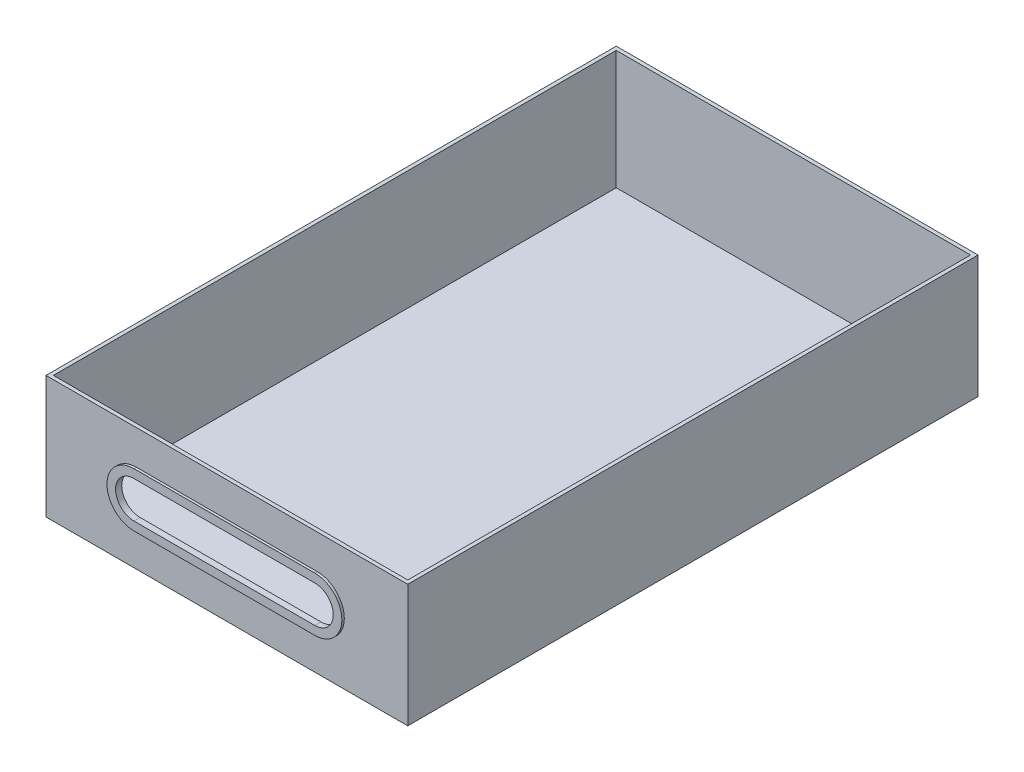
SolidWorks part; units mm, degrees
material "Oak"
ref_plane "Ön Düzlem" through (0, 0, 0) normal (0, 0, 1) x (1, 0, 0)
ref_plane "Üst Düzlem" through (0, 0, 0) normal (0, 1, 0) x (1, 0, 0)
ref_plane "Sağ Düzlem" through (0, 0, 0) normal (1, 0, 0) x (0, 0, -1)
sketch "Sketch2" plane through (0, 0, 0) normal (0, 1, 0) x (1, 0, 0)
  line L0 (-147.5, 232.5) -> (-147.5, -232.5)
  line L1 (-147.5, -232.5) -> (147.5, -232.5)
  line L2 (147.5, -232.5) -> (147.5, 232.5)
  line L3 (147.5, 232.5) -> (-147.5, 232.5)
  point P3 (0, -232.5)
  point P5 (0, 232.5)
  point P7 (147.5, 0)
  dimension "D1" = 465
  dimension "D2" = 295
extrude "Boss-Extrude1" add sketch "Sketch2" against normal blind 100
sketch "Sketch3" plane through (0, 0, 232.5) normal (0, 0, 1) x (1, 0, 0)
  line L0 (-73.75, -50) -> (73.75, -50) construction
  line L1 (-73.75, -28) -> (73.75, -28)
  line L2 (-73.75, -72) -> (73.75, -72)
  line L5 (-845, -50) -> (49155, -50) construction
  line L6 (147.5, -100) -> (147.5, 0) construction
  line L7 (-147.5, 0) -> (0, 0)
  line L8 (-73.75, -50) -> (73.75, -50) construction
  line L9 (-73.75, -35) -> (73.75, -35)
  line L10 (-73.75, -65) -> (73.75, -65)
  arc A0 (-73.75, -28) -> (-73.75, -72) centre (-73.75, -50) ccw
  arc A1 (73.75, -72) -> (73.75, -28) centre (73.75, -50) ccw
  arc A2 (-73.75, -35) -> (-73.75, -65) centre (-73.75, -50) ccw
  arc A3 (73.75, -65) -> (73.75, -35) centre (73.75, -50) ccw
  point P2 (0, -50)
  point P11 (-73.75, 0)
  point P16 (147.5, -50)
  point P19 (0, -50)
  dimension "D1" = 22
  dimension "D2" = 15
shell "Shell5" thickness 3 removed face at (0, 0, 0)
extrude "Cut-Extrude5" cut sketch "Sketch3" against normal up to surface (462 mm away) contours L9 A3 L10 A2 up to face at (0, -48.5, -229.5)
extrude "Boss-Extrude2" add sketch "Sketch3<4>" along normal blind 2 contours L10 A3 L9 A2 | A0 L2 A1 L1 region at (0, -50, 232.5)
sketch "Sketch3<4>" plane through (0, 0, 232.5) normal (0, 0, 1) x (1, 0, 0) same geometry as "Sketch3"
